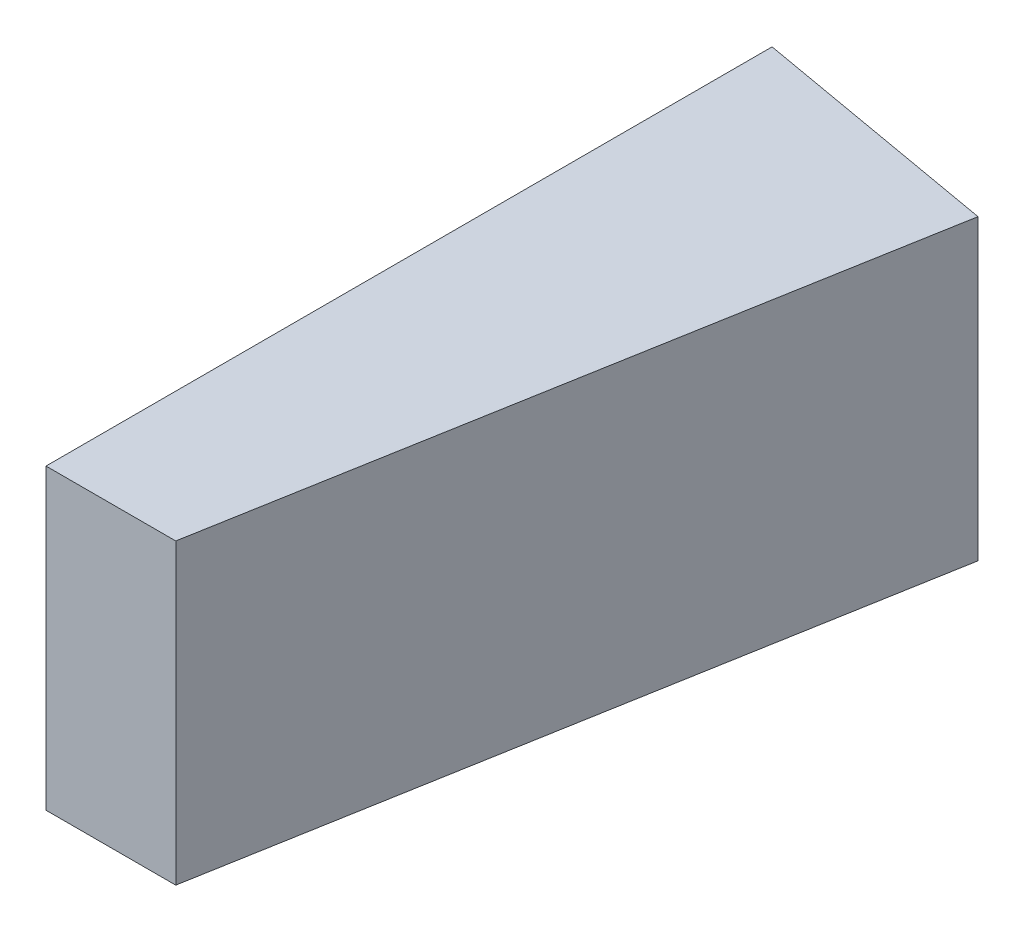
SolidWorks part; units mm, degrees
ref_plane "Front Plane" through (0, 0, 0) normal (0, 0, 1) x (1, 0, 0)
ref_plane "Top Plane" through (0, 0, 0) normal (0, 1, 0) x (1, 0, 0)
ref_plane "Right Plane" through (0, 0, 0) normal (1, 0, 0) x (0, 0, -1)
sketch "Sketch1" plane through (0, 0, 0) normal (0, 1, 0) x (1, 0, 0)
  line L0 (0, 0) -> (0, 24.3577)
  line L1 (0, 24.3577) -> (8.3872, 22.8788)
  line L3 (0, 0) -> (4.353, 0)
  line L4 (4.353, 0) -> (8.3872, 22.8788)
  line L7 (6.425, 11.7505) -> (0.2257, -23.4071) construction
extrude "Boss-Extrude1" add sketch "Sketch1" along normal blind 10
